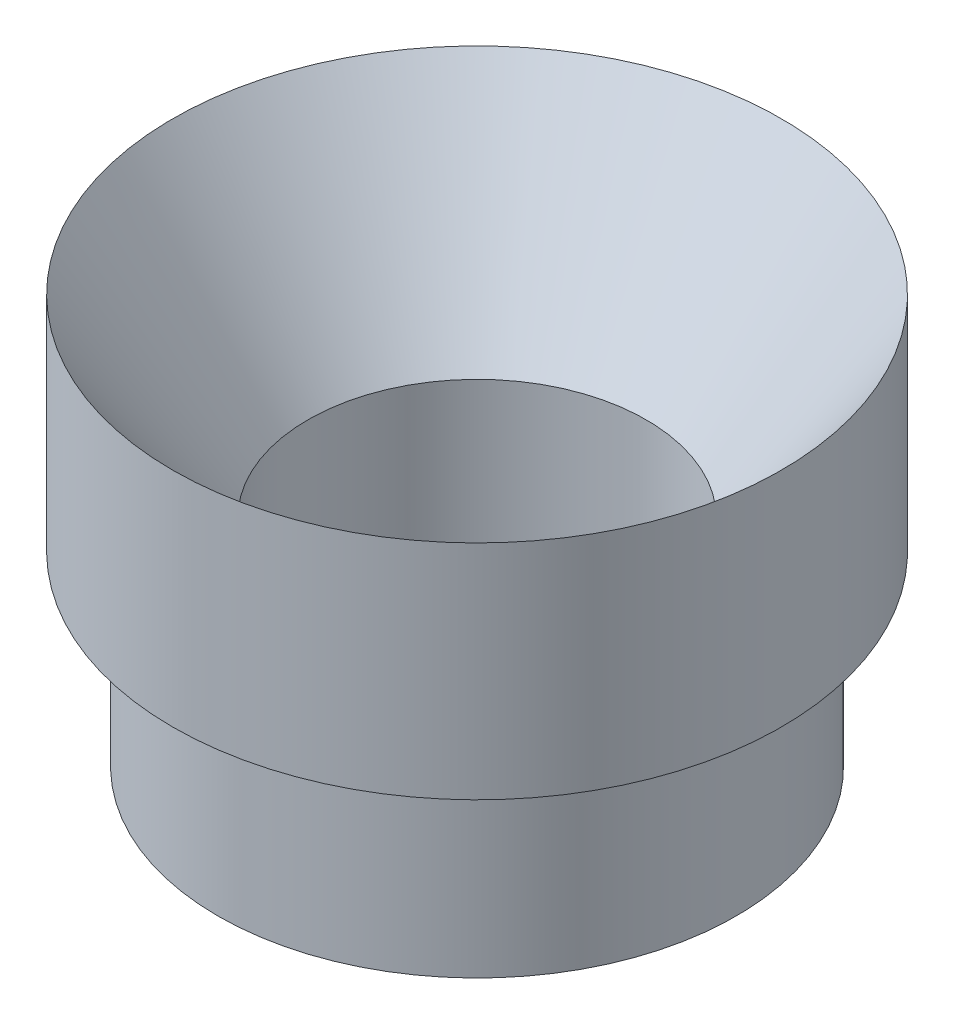
SolidWorks part; units mm, degrees
material "C (Graphite)"
ref_plane "Front Plane" through (0, 0, 0) normal (0, 0, 1) x (1, 0, 0)
ref_plane "Top Plane" through (0, 0, 0) normal (0, 1, 0) x (1, 0, 0)
ref_plane "Right Plane" through (0, 0, 0) normal (1, 0, 0) x (0, 0, -1)
sketch "Sketch4" plane through (0, 0, 0) normal (1, 0, 0) x (0, 0, -1)
  line L0 (0, 0) -> (0, -131.2074) construction
  line L1 (34.2773, 0) -> (23.8732, -14.8586) construction
  line L2 (19.05, -81.8573) -> (19.05, -89.5311) construction
  line L3 (22.2956, -54.8084) -> (51.1382, -162.4506) construction
  line L4 (34.2773, 0) -> (19.05, -21.7468)
  line L17 (34.2773, 0) -> (34.2773, -25.0505)
  line L18 (34.2773, -25.0505) -> (29.1846, -25.0505)
  line L19 (29.1846, -25.0505) -> (29.1846, -46.0309)
  line L20 (29.1846, -46.0309) -> (20.3822, -46.0309)
  line L22 (20.3822, -46.0309) -> (19.05, -38.1493)
  line L24 (19.05, -21.7468) -> (19.05, -38.1493)
  arc A1 (23.8732, -14.8586) -> (19.05, -30.1559) centre (45.72, -30.1559) ccw construction
  arc A2 (19.05, -30.1559) -> (22.2956, -54.8084) centre (114.3, -30.1559) ccw construction
  dimension "D4" = 26.67
  dimension "D6" = 95.25
  dimension "D3" = 35
  dimension "D5" = 38.1
  dimension "D7" = 15
  dimension "D15" = 3.2456
  dimension "D19" = 10.1346
  dimension "D20" = 5.1054
  dimension "D21" = 15.875
  dimension "D11" = 68.5546
  dimension "D24" = 58.3692
revolve "Revolve1" add sketch "Sketch4" angle 360 about L0
sketch "Sketch6" plane through (0, 0, 0) normal (1, 0, 0) x (0, 0, -1)
  line L0 (34.2773, -6.35) -> (32.766, -6.35)
  line L1 (32.766, -6.35) -> (32.766, -8.255)
  line L2 (32.766, -8.255) -> (34.2773, -8.255)
  line L3 (34.2773, -8.255) -> (34.2773, -6.35)
  line L4 (-34.2773, 0) -> (34.2773, 0) construction
  line L5 (-34.2773, 0) -> (34.2773, 0) construction
  line L6 (0, 11.3644) -> (0, 4.9299) construction
  dimension "D1" = 65.532
  dimension "D2" = 1.905
  dimension "D3" = 6.35
revolve "Spring Groove" [suppressed] cut sketch "Sketch6" angle 360 about L6
fillet "Tool Radius" [suppressed] radius 0.4064
equation "\"Dc\"= 114.30mm"
equation "\"Dt\"= 38.1mm"
equation "\"R1\"= 26.67mm"
equation "\"R2\"= 92mm"
equation "\"b\"= 35deg"
equation "\"Rn\"= 95.25mm"
equation "\"Tn\"= 15deg"
equation "\"Te\"= 3deg"
equation "\"De\"= 87.31mm"
equation "\"Le\"= 146.71mm"
equation "\"D5@Sketch4\"=\"Dt\""
equation "\"WallThickness\"=0.5"
equation "\"D20@Sketch4\"=0.200in+.001in"
equation "\"Rt\"=1.5"
